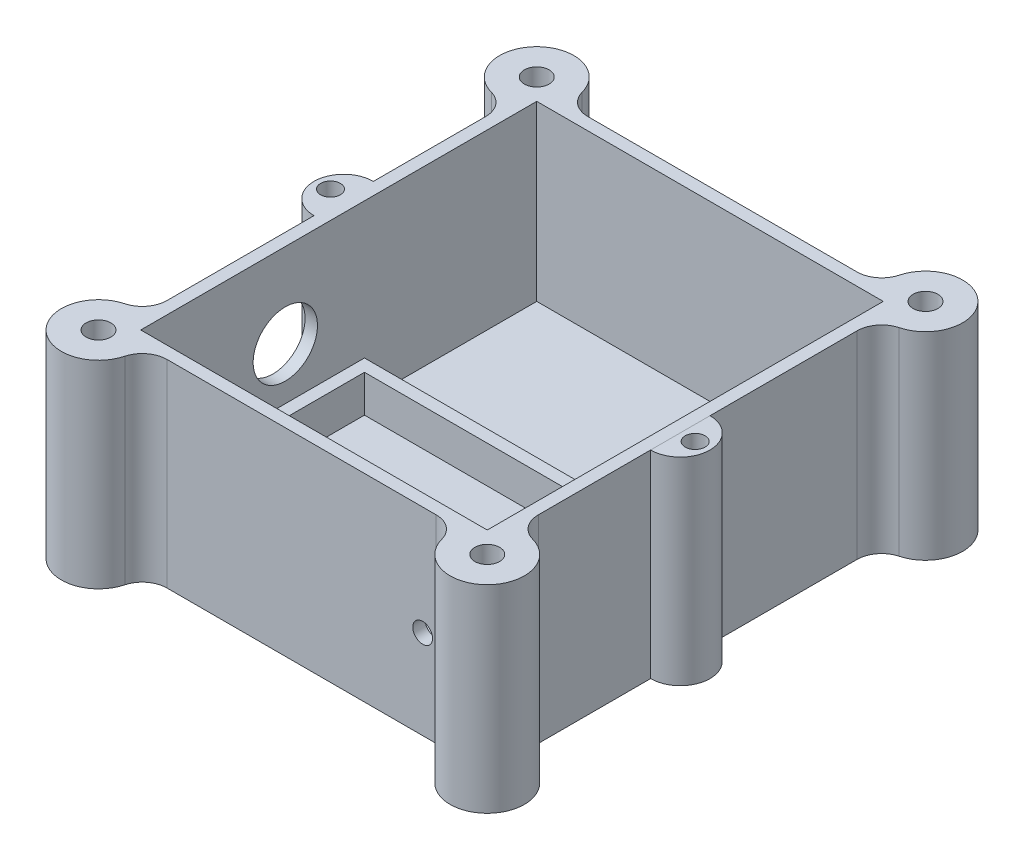
SolidWorks part; units mm, degrees
ref_plane "Front Plane" through (0, 0, 0) normal (0, 0, 1) x (1, 0, 0)
ref_plane "Top Plane" through (0, 0, 0) normal (0, 1, 0) x (1, 0, 0)
ref_plane "Right Plane" through (0, 0, 0) normal (1, 0, 0) x (0, 0, -1)
sketch "Sketch1" plane through (0, 0, 0) normal (0, 1, 0) x (1, 0, 0)
  line L0 (-97.4951, 2.2451) -> (-95.25, 0) construction
  line L1 (-7.0116, 0) -> (-88.2384, 0)
  line L2 (0, -7.0116) -> (0, -100.9384)
  line L3 (-7.0116, -107.95) -> (-88.2384, -107.95)
  line L4 (-95.25, -7.0116) -> (-95.25, -100.9384)
  line L5 (-3.175, -3.175) -> (-92.075, -3.175)
  line L6 (-3.175, -3.175) -> (-3.175, -104.775)
  line L7 (-3.175, -104.775) -> (-92.075, -104.775)
  line L8 (-92.075, -3.175) -> (-92.075, -104.775)
  line L9 (2.2451, 2.2451) -> (0, 0) construction
  line L10 (2.2451, -110.1951) -> (0, -107.95) construction
  line L11 (-97.4951, -110.1951) -> (-95.25, -107.95) construction
  circle A0 centre (-97.4951, 2.2451) radius 3.175
  arc A1 (-88.2384, 0) -> (-95.25, -7.0116) centre (-97.4951, 2.2451) ccw
  circle A2 centre (2.2451, 2.2451) radius 3.175
  arc A3 (0, -7.0116) -> (-7.0116, 0) centre (2.2451, 2.2451) ccw
  circle A4 centre (2.2451, -110.1951) radius 3.175
  arc A5 (-7.0116, -107.95) -> (0, -100.9384) centre (2.2451, -110.1951) ccw
  circle A6 centre (-97.4951, -110.1951) radius 3.175
  arc A7 (-95.25, -100.9384) -> (-88.2384, -107.95) centre (-97.4951, -110.1951) ccw
  dimension "D11" = 6.35
  dimension "D12" = 6.35
  dimension "D13" = 6.35
  dimension "D14" = 6.35
  dimension "D15" = 6.35
  dimension "D16" = 6.35
  dimension "D17" = 6.35
  dimension "D18" = 6.35
  dimension "D1" = 107.95
  dimension "D2" = 95.25
  dimension "D3" = 88.9
  dimension "D4" = 101.6
  dimension "D5" = 3.175
  dimension "D6" = 3.175
  dimension "D7" = 135
  dimension "D8" = 135
  dimension "D9" = 135
  dimension "D10" = 135
extrude "Boss-Extrude1" add sketch "Sketch1" along normal blind 6.35 contours L4 A7 L3 A5 L2 A3 L1 A1 | A2 | A4 | A6 | A0
extrude "Boss-Extrude2" add sketch "Sketch1<3>" along normal blind 50.8
sketch "Sketch1<3>" plane through (0, 0, 0) normal (0, 1, 0) x (1, 0, 0) same geometry as "Sketch1"
sketch "Sketch3" plane through (0, 0, 107.95) normal (0, 0, 1) x (1, 0, 0)
  line L0 (-7.0116, 0) -> (-88.2384, 0) construction
  line L1 (0, 50.8) -> (0, 0) construction
  circle A0 centre (-16.5661, 22.86) radius 2.54
  dimension "D1" = 5.08
  dimension "D2" = 22.86
  dimension "D3" = 16.5661
extrude "Cut-Extrude1" cut sketch "Sketch3" against normal blind 12.7
sketch "Sketch5" plane through (0, 0, 0) normal (1, 0, 0) x (0, 0, -1)
  line L0 (-100.9384, 50.8) -> (-7.0116, 50.8) construction
  line L1 (-66.04, 50.8) -> (-58.42, 50.8)
  line L2 (-66.04, 50.8) -> (-66.04, 0)
  line L3 (-66.04, 0) -> (-58.42, 0)
  line L4 (-58.42, 50.8) -> (-58.42, 0)
  line L5 (-7.0116, 0) -> (-100.9384, 0) construction
  dimension "D1" = 7.62
revolve "Revolve1" add sketch "Sketch5" angle 180 about L4 reverse direction yes
sketch "Sketch6" plane through (-95.25, 0, 0) normal (-1, 0, 0) x (0, 0, 1)
  line L0 (7.0116, 50.8) -> (100.9384, 50.8) construction
  line L1 (49.53, 50.8) -> (57.15, 50.8)
  line L2 (49.53, 50.8) -> (49.53, 0)
  line L3 (49.53, 0) -> (57.15, 0)
  line L4 (57.15, 50.8) -> (57.15, 0)
  line L5 (7.0116, 0) -> (100.9384, 0) construction
  dimension "D1" = 7.62
revolve "Revolve2" add sketch "Sketch6" angle 180 about L2
sketch "Sketch7" plane through (0, 50.8, 0) normal (0, 1, 0) x (1, 0, 0)
  circle A0 centre (-99.039, -49.1303) radius 2.54
  arc A9 (-95.25, -41.91) -> (-95.25, -57.15) centre (-95.25, -49.53) ccw construction
  dimension "D1" = 5.08
  dimension "D2" = 3.81
  dimension "D3" = 3.789
extrude "Cut-Extrude2" cut sketch "Sketch7" against normal through all
sketch "Sketch9" plane through (0, 50.8, 0) normal (0, 1, 0) x (1, 0, 0)
  line L0 (0, -100.9384) -> (0, -7.0116) construction
  circle A0 centre (3.81, -58.42) radius 2.54
  arc A1 (0, -66.04) -> (0, -50.8) centre (0, -58.42) ccw construction
  dimension "D1" = 5.08
  dimension "D2" = 3.81
  dimension "D3" = 3.81
extrude "Cut-Extrude3" cut sketch "Sketch9" against normal through all
sketch "Sketch10" plane through (0, 6.35, 0) normal (0, 1, 0) x (1, 0, 0)
  line L0 (-92.075, -104.775) -> (-92.075, -3.175) construction
  line L1 (-92.075, -104.775) -> (-3.175, -104.775)
  line L2 (-92.075, -104.775) -> (-92.075, -47.371)
  line L3 (-92.075, -47.371) -> (-3.175, -47.371)
  line L4 (-3.175, -104.775) -> (-3.175, -47.371)
  line L6 (-88.9, -101.6) -> (-7.366, -101.6)
  line L7 (-88.9, -101.6) -> (-88.9, -50.546)
  line L8 (-88.9, -50.546) -> (-7.366, -50.546)
  line L9 (-7.366, -101.6) -> (-7.366, -50.546)
  dimension "D1" = 3.175
  dimension "D2" = 3.175
  dimension "D3" = 3.175
  dimension "D4" = 4.191
  dimension "D5" = 51.054
  dimension "D6" = 81.534
extrude "Boss-Extrude3" add sketch "Sketch10" along normal blind 9.525
sketch "Sketch11" plane through (0, 6.35, 0) normal (0, 1, 0) x (1, 0, 0)
  line L0 (-73.533, -74.4855) -> (-73.533, -50.546) construction
  line L1 (-22.733, -74.4855) -> (-73.533, -74.4855)
  line L2 (-22.733, -74.4855) -> (-22.733, -77.6605)
  line L3 (-22.733, -77.6605) -> (-73.533, -77.6605)
  line L4 (-73.533, -74.4855) -> (-73.533, -77.6605)
  line L5 (-7.366, -50.546) -> (-88.9, -50.546) construction
  line L6 (-73.533, -77.6605) -> (-73.533, -101.6) construction
  line L7 (-88.9, -101.6) -> (-7.366, -101.6) construction
  line L8 (-73.533, -75.356) -> (-88.9, -75.356) construction
  line L9 (-88.9, -50.546) -> (-88.9, -101.6) construction
  line L10 (-22.733, -75.356) -> (-7.366, -75.356) construction
  line L11 (-7.366, -101.6) -> (-7.366, -50.546) construction
  dimension "D1" = 3.175
  dimension "D2" = 50.8
extrude "Boss-Extrude4" add sketch "Sketch11" along normal blind 5.08
sketch "Sketch12" plane through (-95.25, 0, 0) normal (-1, 0, 0) x (0, 0, 1)
  line L1 (57.15, 0) -> (100.9384, 0) construction
  line L2 (57.15, 0) -> (57.15, 50.8) construction
  circle A0 centre (67.691, 29.1465) radius 8.255
  dimension "D1" = 16.51
  dimension "D2" = 10.541
  dimension "D3" = 29.1465
extrude "Cut-Extrude4" cut sketch "Sketch12" against normal blind 7.62
fillet "Fillet1" radius 3.175 4 edges at (-97.4951, 0, 113.3701) (2.2451, 0, 113.3701) (-97.4951, 0, 0.9299) (2.2451, 0, 0.9299)
fillet "Fillet2" radius 6.35 8 edges at (0, 25.4, 7.0116) (0, 25.4, 100.9384) (-95.25, 25.4, 100.9384) (-95.25, 25.4, 7.0116) (-88.2384, 25.4, 107.95) (-7.0116, 25.4, 107.95) (-88.2384, 25.4, 0) (-7.0116, 25.4, 0)
